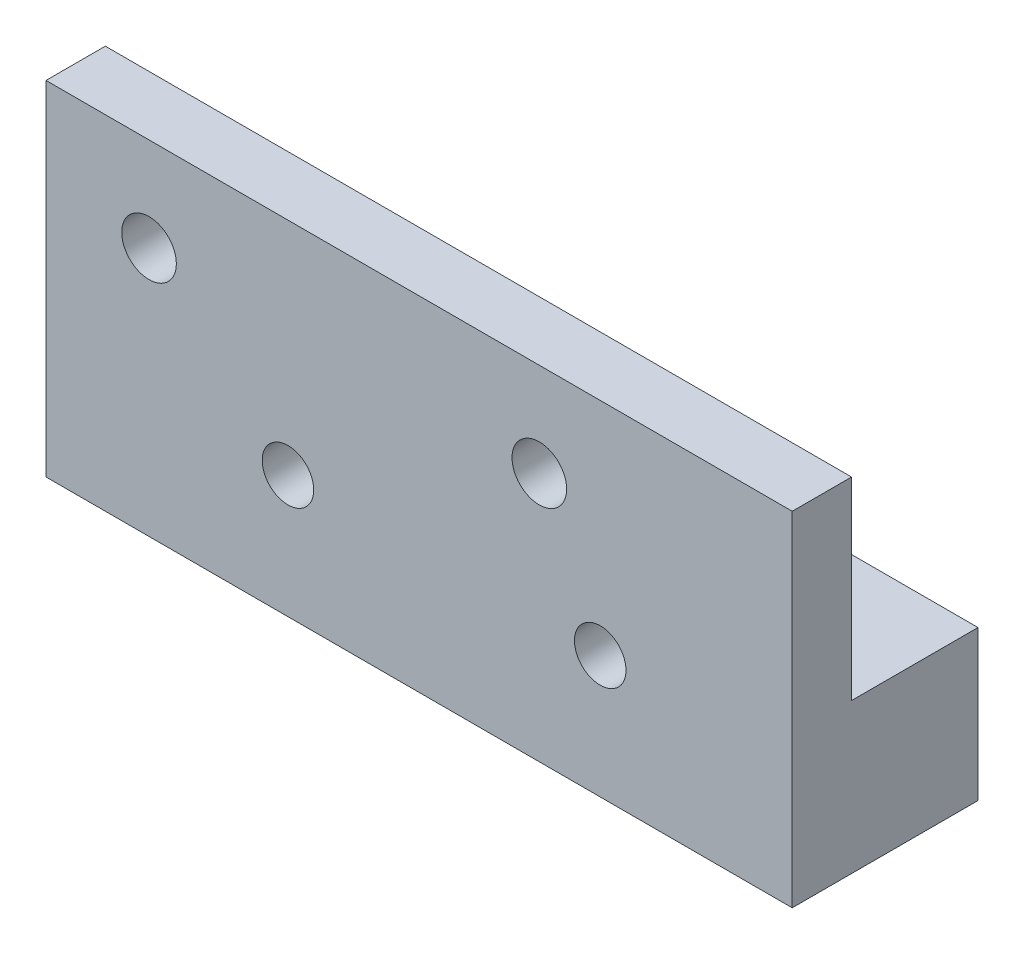
SolidWorks part; units mm, degrees
ref_plane "Front Plane" through (0, 0, 0) normal (0, 0, 1) x (1, 0, 0)
ref_plane "Top Plane" through (0, 0, 0) normal (0, 1, 0) x (1, 0, 0)
ref_plane "Right Plane" through (0, 0, 0) normal (1, 0, 0) x (0, 0, -1)
sketch "Croquis2" plane through (0, 0, 0) normal (0, 0, 1) x (1, 0, 0)
  line L1 (-61.65, -21.1) -> (-13.85, -21.1)
  line L6 (-61.65, -21.1) -> (-61.65, -30.7)
  line L7 (-9.25, -32.7) -> (8.75, -32.7) construction
  line L8 (-9.25, -32.7) -> (8.75, -32.7) construction
  line L10 (-61.65, -21.1) -> (-13.85, -21.1) construction
  line L11 (-61.65, -8.55) -> (-61.65, -30.7) construction
  line L12 (-390.05, -20.7) -> (-20.05, -20.7) construction
  line L13 (-13.85, -21.1) -> (-13.85, -30.7)
  line L14 (-61.65, -30.7) -> (-13.85, -30.7)
  line L15 (-13.65, -30.7) -> (-13.65, -8.55) construction
  line L21 (-61.65, -30.7) -> (-13.65, -30.7) construction
  dimension "D1" = 0.2
  dimension "D2" = 0.4
extrude "Saliente-Extruir2" add sketch "Croquis2" along normal offset from surface (11.9 mm away) 4 from offset 0.1 offset beyond the face yes
sketch "Croquis3" plane through (0, -30.7, 0) normal (0, -1, 0) x (1, 0, 0)
  line L0 (-13.85, 12) -> (-13.85, 0.1) construction
  line L1 (-61.65, 12) -> (-13.85, 12)
  line L2 (-61.65, 12) -> (-61.65, 8.2)
  line L3 (-61.65, 8.2) -> (-13.85, 8.2)
  line L4 (-13.85, 12) -> (-13.85, 8.2)
  line L6 (-390.05, 8) -> (-20.05, 8) construction
  line M2 (-13.85, 0.1) -> (-13.85, 12)
  line M3 (-13.85, 12) -> (-61.65, 12)
  dimension "D1" = 0.2
extrude "Saliente-Extruir3" add sketch "Croquis3" against normal up to surface (22 mm away) contours L3 M2 M3 | L3 region at (-37.75, -30.7, 10.1)
sketch "Croquis5" plane through (0, 0, 12) normal (0, 0, 1) x (1, 0, 0)
  circle A0 centre (-30.05, -14.7) radius 1.75 construction
  circle A1 centre (-30.05, -14.7) radius 1.75
  circle A2 centre (-55.05, -14.7) radius 1.75 construction
  circle A3 centre (-55.05, -14.7) radius 1.75
  circle A4 centre (-46.15, -22.85) radius 1.65 construction
  circle A5 centre (-46.15, -22.85) radius 1.65
  circle A6 centre (-26.15, -22.85) radius 1.65 construction
  circle A7 centre (-26.15, -22.85) radius 1.65
extrude "Cortar-Extruir1" cut sketch "Croquis5" against normal up to next
